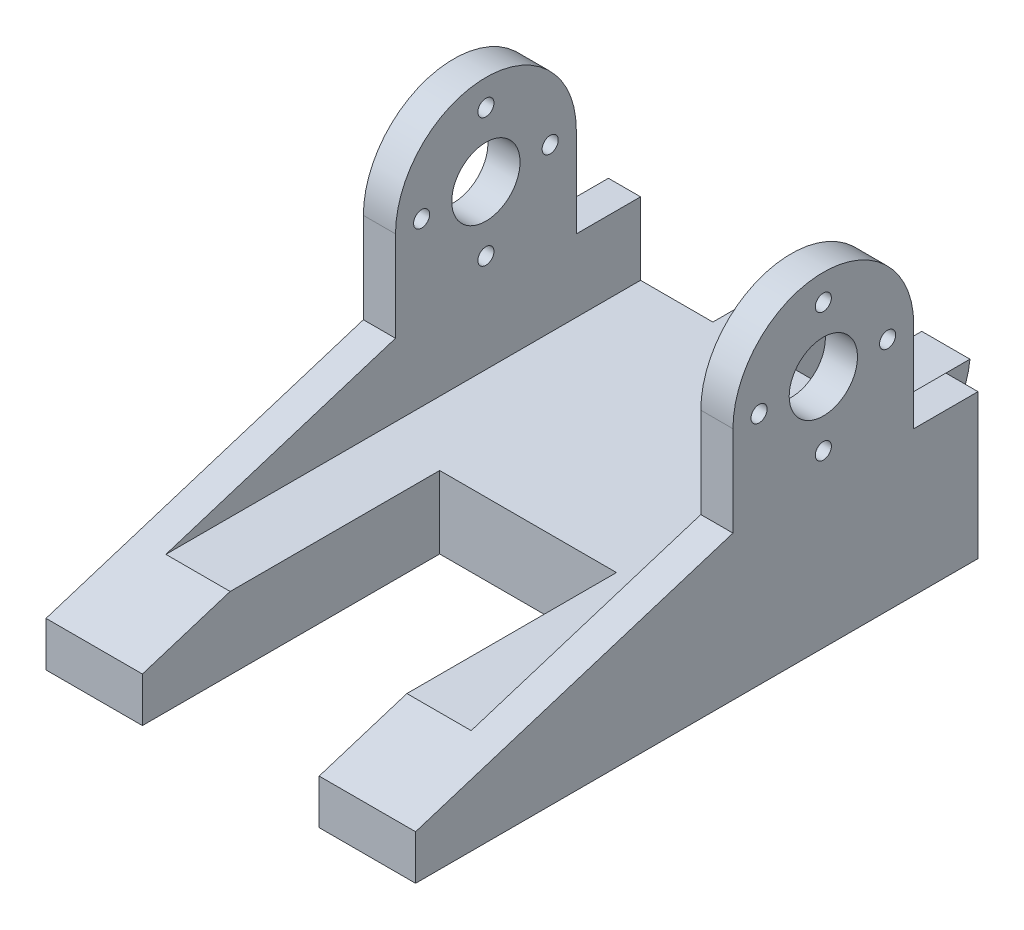
SolidWorks part; units mm, degrees
ref_plane "Front Plane" through (0, 0, 0) normal (0, 0, 1) x (1, 0, 0)
ref_plane "Top Plane" through (0, 0, 0) normal (0, 1, 0) x (1, 0, 0)
ref_plane "Right Plane" through (0, 0, 0) normal (1, 0, 0) x (0, 0, -1)
sketch "Sketch1" plane through (0, 0, 0) normal (0, 0, 1) x (1, 0, 0)
  line L1 (-25, 0) -> (25, 0)
  line L2 (-25, 0) -> (-25, -170)
  line L3 (-25, -170) -> (25, -170)
  line L4 (25, 0) -> (25, -170)
  dimension "D1" = 170
  dimension "D2" = 50
extrude "Boss-Extrude1" add sketch "Sketch1" against normal blind 55
sketch "Sketch2" plane through (0, 0, 0) normal (0, 0, 1) x (1, 0, 0)
  line L0 (25, 0) -> (-25, 0) construction
  line L1 (-17, 0) -> (17, 0)
  line L2 (-17, 0) -> (-17, -27)
  line L3 (-17, -27) -> (17, -27)
  line L4 (17, 0) -> (17, -27)
  line L5 (-25, 0) -> (-25, -170) construction
  dimension "D1" = 8
  dimension "D2" = 34
  dimension "D3" = 27
extrude "Cut-Extrude1" cut sketch "Sketch2" against normal through all
sketch "Sketch3" plane through (25, 0, 0) normal (1, 0, 0) x (0, 0, -1)
  line L0 (0, -170) -> (0, 0) construction
  line L1 (55, -27) -> (0, -27)
  line L2 (55, -27) -> (55, -24)
  line L3 (55, -24) -> (0, -24)
  line L4 (0, -27) -> (0, -24)
  line L5 (55, -170) -> (55, 0) construction
  line L7 (0, 0) -> (10, 0)
  line L8 (0, 0) -> (0, -24)
  line L9 (0, -24) -> (10, -24)
  line L10 (10, 0) -> (10, -24)
  line L11 (55, 0) -> (45, 0)
  line L12 (55, 0) -> (55, -24)
  line L13 (55, -24) -> (45, -24)
  line L14 (45, 0) -> (45, -24)
  circle A0 centre (27.5, -12.75) radius 10.25
  circle A1 centre (27.5, -12.75) radius 4.25
  circle A2 centre (27.5, -12.75) radius 8
  circle A3 centre (27.5, -4.75) radius 1
  circle A4 centre (35.5, -12.75) radius 1
  circle A5 centre (27.5, -20.75) radius 1
  circle A6 centre (19.5, -12.75) radius 1
  point P32 (27.5, -12.75)
  line M7 (0, 0) -> (0, -170)
  line M9 (55, -170) -> (55, 0)
  line M10 (55, 0) -> (0, 0)
  dimension "D2" = 11.25
  dimension "D3" = 27.5
  dimension "D4" = 20.5
  dimension "D7" = 8.5
  dimension "D8" = 16
  dimension "D9" = 4
  dimension "D1" = 3
  dimension "D5" = 10
  dimension "D6" = 10
extrude "Cut-Extrude2" cut sketch "Sketch3" against normal through all contours L14 L3 M10 M9 | L10 L3 M10 M7 | A2 A6 | A2 A6 | A1 | A2 A5 | A2 A5 | A2 A4 | A2 A4 | A2 A3 | A2 A3 region at (25, -12, -50) region at (25, -12, -5) region at (25, -12.75, -27.5) region at (25, -12.75, -35.0645) region at (25, -12.75, -35.913) region at (25, -5.1855, -27.5) region at (25, -4.337, -27.5) region at (25, -21.163, -27.5) region at (25, -20.3145, -27.5) region at (25, -12.75, -19.9355) region at (25, -12.75, -19.087)
sketch "Sketch4" plane through (0, 0, -10) normal (0, 0, 1) x (1, 0, 0)
  line L0 (-25, -24) -> (-17, -24) construction
  line L1 (-17, 0) -> (-19, 0)
  line L2 (-17, 0) -> (-17, -24)
  line L3 (-17, -24) -> (-19, -24)
  line L4 (-19, 0) -> (-19, -24)
  line L5 (0, 0) -> (0, -13.53) construction
  line L6 (19, 0) -> (19, -24)
  line L7 (17, -24) -> (19, -24)
  line L8 (17, 0) -> (17, -24)
  line L9 (17, 0) -> (19, 0)
  dimension "D1" = 2
extrude "Cut-Extrude3" cut sketch "Sketch4" against normal through all
sketch "Sketch5" plane through (25, 0, 0) normal (1, 0, 0) x (0, 0, -1)
  line L1 (10, 0) -> (45, 0)
  line L2 (10, 0) -> (10, -24)
  line L3 (10, -24) -> (45, -24)
  line L4 (45, 0) -> (45, -24)
  line L5 (38.75, -12.75) -> (38.75, -24)
  line L6 (16.25, -12.75) -> (10, -12.75)
  line L7 (16.25, -12.75) -> (16.25, -24)
  line L8 (16.25, -24) -> (10, -24)
  line L9 (10, -12.75) -> (10, -24)
  line L10 (38.75, -12.75) -> (45, -12.75)
  line L11 (38.75, -12.75) -> (38.75, -24)
  line L12 (38.75, -24) -> (45, -24)
  line L13 (45, -12.75) -> (45, -24)
  circle A0 centre (27.5, -12.75) radius 11.25
  line M8 (45, -24) -> (45, 0)
  line M9 (45, 0) -> (10, 0)
  line M10 (10, 0) -> (10, -24)
  dimension "D1" = 22.5
extrude "Cut-Extrude4" cut sketch "Sketch5" against normal through all contours A0 L10 L4 L6 M9 M10 | L7 L6 L2 L3 | L10 L5 L3 M8 region at (25, -0.3725, -27.5) region at (25, -18.375, -13.125) region at (25, -18.375, -41.875)
sketch "Sketch6" plane through (0, 0, 0) normal (0, 0, 1) x (1, 0, 0)
  line L1 (-19, -24) -> (19, -24)
  line L2 (-19, -24) -> (-19, -34)
  line L3 (-19, -34) -> (19, -34)
  line L4 (19, -24) -> (19, -34)
  dimension "D1" = 10
extrude "Cut-Extrude5" cut sketch "Sketch6" against normal through all
sketch "Sketch8" plane through (25, 0, 0) normal (1, 0, 0) x (0, 0, -1)
  line L0 (55, -170) -> (55, -24) construction
  line L1 (0, -170) -> (0, -24) construction
  line L2 (41.75, -132.5) -> (13.25, -132.5)
  line L3 (27.5, -132.5) -> (27.5, -179)
  line L4 (41.75, -179) -> (13.25, -179)
  line L5 (13.25, -132.5) -> (13.25, -179)
  line L7 (41.75, -132.5) -> (41.75, -179)
  line L11 (27.5, -167.75) -> (55, -167.75)
  line L12 (27.5, -167.75) -> (27.5, -170)
  line L13 (27.5, -170) -> (55, -170)
  line L14 (55, -167.75) -> (55, -170)
  line L16 (27.5, -167.75) -> (0, -167.75)
  line L17 (27.5, -167.75) -> (27.5, -170)
  line L18 (27.5, -170) -> (0, -170)
  line L19 (0, -167.75) -> (0, -170)
  circle A0 centre (27.5, -167.75) radius 10.25
  circle A1 centre (27.5, -12.75) radius 10.25
  line M4 (0, -24) -> (0, -170)
  line M5 (0, -170) -> (55, -170)
  line M6 (55, -170) -> (55, -24)
  dimension "D1" = 27.5
  dimension "D2" = 20.5
  dimension "D3" = 155
  dimension "D4" = 14.25
  dimension "D5" = 11.25
  dimension "D6" = 46.5
  dimension "D7" = 13.25
extrude "Cut-Extrude7" cut sketch "Sketch8" against normal through all contours A0 L3 L2 L5 L16 | A0 L11 L7 L2 L3 | L11 L7 M5 M6 | L5 L16 M4 M5 | A0 L16 L5 M5 | A0 L13 L7 L11 | L3 A0 L16 | L11 A0 L3 | L16 A0 L18 L3 | A0 L11 L3 M5 region at (25, -147.5157, -35.1704) region at (25, -147.5157, -19.8296) region at (25, -168.875, -48.375) region at (25, -168.8865, -39.7079) region at (25, -163.3998, -31.8502) region at (25, -163.3998, -23.1498) region at (25, -168.8704, -32.5838) region at (25, -168.8865, -15.2921) region at (25, -168.875, -6.625) region at (25, -168.8704, -22.4162)
sketch "Sketch9" plane through (0, 0, 0) normal (0, 0, 1) x (1, 0, 0)
  line L0 (-25, -167.75) -> (25, -167.75) construction
  line L1 (17, -167.75) -> (-17, -167.75)
  line L2 (17, -167.75) -> (17, -132.5)
  line L3 (17, -132.5) -> (-17, -132.5)
  line L4 (-17, -167.75) -> (-17, -132.5)
  line L5 (-25, -132.5) -> (25, -132.5) construction
  line L7 (-25, -24) -> (-25, -167.75) construction
  line L9 (25, -167.75) -> (25, -24) construction
  dimension "D1" = 8
  dimension "D2" = 8
extrude "Cut-Extrude8" cut sketch "Sketch9" against normal through all
sketch "Sketch11" plane through (25, 0, 0) normal (1, 0, 0) x (0, 0, -1)
  line L0 (27.5, -157.5) -> (27.5, -147.5)
  line L2 (27.5, -147.5) -> (55, -147.5)
  line L3 (27.5, -147.5) -> (27.5, -167.75)
  line L4 (27.5, -167.75) -> (55, -167.75)
  line L5 (55, -147.5) -> (55, -167.75)
  line L6 (27.5, -147.5) -> (0, -147.5)
  line L7 (27.5, -147.5) -> (27.5, -167.75)
  line L8 (27.5, -167.75) -> (0, -167.75)
  line L9 (0, -147.5) -> (0, -167.75)
  circle A0 centre (27.5, -167.75) radius 10.25
  arc A1 (38.75, -12.75) -> (16.25, -12.75) centre (27.5, -12.75) ccw construction
  line M1 (0, -167.75) -> (13.25, -167.75)
  line M2 (13.25, -167.75) -> (13.25, -132.5)
  line M4 (41.75, -132.5) -> (41.75, -167.75)
  line M5 (41.75, -167.75) -> (55, -167.75)
  line M6 (55, -167.75) -> (55, -24)
  line M12 (0, -24) -> (0, -167.75)
  dimension "D1" = 155
  dimension "D2" = 20.5
  dimension "D3" = 10
extrude "Cut-Extrude9" cut sketch "Sketch11" against normal through all contours A0 L0 L6 L8 M2 | A0 L4 L2 L0 M4 | L2 M4 M5 M6 | L6 M2 M12 M1 region at (25, -155.3124, -19.2638) region at (25, -155.3124, -35.7362) region at (25, -157.625, -48.375) region at (25, -157.625, -6.625)
sketch "Sketch12" plane through (25, 0, 0) normal (1, 0, 0) x (0, 0, -1)
  line L1 (13.25, -132.5) -> (41.75, -132.5)
  line L2 (13.25, -132.5) -> (13.25, -147.5)
  line L3 (13.25, -147.5) -> (41.75, -147.5)
  line L4 (41.75, -132.5) -> (41.75, -147.5)
extrude "Boss-Extrude2" add sketch "Sketch12" against normal blind 8
ref_plane "Plane1" through (0, 0, 0) normal (1, 0, 0) x (0, 0, -1)
mirror "Mirror1" about plane through (0, 0, 0) normal (1, 0, 0) of "Boss-Extrude2"
sketch "Sketch14" plane through (0, 0, 0) normal (0, 0, 1) x (1, 0, 0)
  line L0 (17, -148.55) -> (17, -158.75) construction
  line L1 (-17, -132.5) -> (17, -132.5)
  line L2 (-17, -132.5) -> (-17, -147.5)
  line L3 (-17, -147.5) -> (17, -147.5)
  line L4 (17, -132.5) -> (17, -147.5)
  line L5 (-17, -147.5) -> (17, -147.5)
  line L6 (-17, -147.5) -> (-17, -157.75)
  line L7 (-17, -157.75) -> (17, -157.75)
  line L8 (17, -147.5) -> (17, -157.75)
  line M11 (-17, -147.5) -> (-17, -132.5)
  line M12 (-17, -132.5) -> (17, -132.5)
  line M13 (17, -132.5) -> (17, -147.5)
  dimension "D1" = 10.25
extrude "Boss-Extrude3" add sketch "Sketch14" against normal blind 13.25 contours L3 M11 M13 M12 | L8 L3 L6 L7 region at (0, -140, 0) region at (0, -152.625, 0)
ref_plane "Plane2" through (0, 0, -27.5) normal (0, 0, 1) x (1, 0, 0)
mirror "Mirror2" about plane through (0, 0, -27.5) normal (0, 0, 1) of "Boss-Extrude3"
sketch "Sketch16" plane through (25, 0, 0) normal (1, 0, 0) x (0, 0, -1)
  line L0 (41.75, -132.5) -> (13.25, -132.5) construction
  line L1 (13.25, -132.5) -> (13.25, -147.5) construction
  circle A1 centre (16.5, -135.75) radius 2.5
  circle A2 centre (16.5, -135.75) radius 4.5
  circle A3 centre (38.5, -135.75) radius 4.5
  dimension "D1" = 3.25
  dimension "D2" = 3.25
  dimension "D3" = 2
extrude "Cut-Extrude13" cut sketch "Sketch16" against normal blind 8 contours A1 | A2 A1 | A3 region at (25, -135.75, -16.5) region at (25, -135.75, -12.1273) region at (25, -135.75, -38.5)
mirror "Mirror3" about plane through (0, 0, 0) normal (1, 0, 0) of "Cut-Extrude13"
sketch "Sketch17" plane through (25, 0, 0) normal (1, 0, 0) x (0, 0, -1)
  line L0 (55, -147.5) -> (55, -24) construction
  line L1 (27.5, -1.5) -> (55, -1.5)
  line L2 (27.5, -1.5) -> (27.5, -51.5)
  line L3 (27.5, -51.5) -> (55, -51.5)
  line L4 (55, -1.5) -> (55, -51.5)
  line L8 (55, -51.5) -> (0, -51.5)
  line L9 (55, -51.5) -> (55, -157.75)
  line L10 (55, -157.75) -> (0, -157.75)
  line L11 (0, -51.5) -> (0, -157.75)
  arc A0 (38.75, -12.75) -> (16.25, -12.75) centre (27.5, -12.75) ccw construction
  circle M2 centre (16.5, -135.75) radius 4.5
  circle M3 centre (38.5, -135.75) radius 4.5
  line M4 (0, -147.5) -> (55, -147.5)
  line M5 (55, -147.5) -> (55, -24)
  line M11 (0, -24) -> (0, -147.5)
  dimension "D1" = 50
extrude "Cut-Extrude15" cut sketch "Sketch17" against normal through all contours L3 L8 M11 M4 M5 M2 M3 | L11 L10 L9 M4 | M3 | M2 region at (25, -98.6049, -27.5) region at (25, -152.625, -27.5) region at (25, -135.75, -16.5) region at (25, -135.75, -38.5)
sketch "Sketch18" plane through (25, 0, 0) normal (1, 0, 0) x (0, 0, -1)
  line L1 (38.75, -24) -> (-71.25, -24)
  line L2 (38.75, -24) -> (38.75, -51.5)
  line L3 (38.75, -51.5) -> (-71.25, -51.5)
  line L4 (-71.25, -24) -> (-71.25, -51.5)
  line L6 (38.75, -24) -> (68.75, -24)
  line L7 (38.75, -24) -> (38.75, -51.5)
  line L8 (38.75, -51.5) -> (68.75, -51.5)
  line L9 (68.75, -24) -> (68.75, -51.5)
  line M8 (0, -24) -> (0, -51.5)
  line M9 (0, -51.5) -> (55, -51.5)
  line M10 (55, -51.5) -> (55, -24)
  line M11 (55, -24) -> (38.75, -24)
  line M15 (16.25, -24) -> (0, -24)
  dimension "D1" = 110
  dimension "D2" = 30
extrude "Boss-Extrude4" add sketch "Sketch18" against normal blind 50 contours L1 L4 L3 M8 | L9 L6 L8 M10 | L2 L1 M15 M8 M9 | L2 M11 M9 M10 region at (25, -37.75, -19.375) region at (25, -37.75, -46.875) region at (25, -37.75, -61.875) region at (25, -37.75, 35.625)
sketch "Sketch19" plane through (0, 0, 71.25) normal (0, 0, 1) x (1, 0, 0)
  line L1 (-19, -24) -> (19, -24)
  line L2 (-19, -24) -> (-19, -31)
  line L3 (-19, -31) -> (19, -31)
  line L4 (19, -24) -> (19, -31)
  dimension "D1" = 7
extrude "Cut-Extrude16" cut sketch "Sketch19" against normal through all
sketch "Sketch20" plane through (25, 0, 0) normal (1, 0, 0) x (0, 0, -1)
  line L1 (-71.25, -24) -> (68.75, -24)
  line L2 (-71.25, -24) -> (-71.25, -51.5)
  line L3 (-71.25, -51.5) -> (68.75, -51.5)
  line L4 (68.75, -24) -> (68.75, -51.5)
  line L5 (16.25, -24) -> (-13.75, -24)
  line L6 (16.25, -24) -> (16.25, -51.5)
  line L7 (16.25, -51.5) -> (-13.75, -51.5)
  line L8 (-13.75, -24) -> (-13.75, -51.5)
  line L10 (-13.75, -51.5) -> (-71.25, -51.5)
  line L11 (-13.75, -51.5) -> (-13.75, -24)
  line L12 (-13.75, -24) -> (-71.25, -24)
  line L13 (-71.25, -51.5) -> (-71.25, -24)
  line M8 (-71.25, -24) -> (-71.25, -51.5)
  line M9 (-71.25, -51.5) -> (68.75, -51.5)
  dimension "D1" = 30
extrude "Cut-Extrude17" cut sketch "Sketch20" against normal through all contours L8 L1 M8 M9 region at (25, -37.75, 42.5)
sketch "Sketch21" plane through (25, 0, 0) normal (1, 0, 0) x (0, 0, -1)
  line L0 (16.25, -24) -> (-13.75, -51.5)
  line L1 (16.25, -24) -> (-13.75, -24)
  line L2 (16.25, -24) -> (16.25, -51.5)
  line L3 (16.25, -51.5) -> (-13.75, -51.5)
  line L4 (-13.75, -24) -> (-13.75, -51.5)
  line M6 (16.25, -24) -> (-13.75, -24)
  line M7 (-13.75, -24) -> (-13.75, -51.5)
extrude "Cut-Extrude18" cut sketch "Sketch21" against normal through all contours L0 M6 M7 region at (25, -33.1667, 3.75)
sketch "Sketch22" plane through (25, 0, 0) normal (1, 0, 0) x (0, 0, -1)
  line L3 (68.75, -51.5) -> (-13.75, -51.5)
  line L4 (68.75, -51.5) -> (68.75, -54)
  line L5 (68.75, -54) -> (-13.75, -54)
  line L6 (-13.75, -51.5) -> (-13.75, -54)
  dimension "D1" = 2.5
extrude "Boss-Extrude5" add sketch "Sketch22" against normal blind 50
sketch "Sketch24" plane through (25, 0, 0) normal (1, 0, 0) x (0, 0, -1)
  line L1 (68.75, -24) -> (46.75, -24)
  line L2 (68.75, -24) -> (68.75, -41)
  line L3 (68.75, -41) -> (46.75, -41)
  line L4 (46.75, -24) -> (46.75, -41)
  dimension "D1" = 17
  dimension "D2" = 22
extrude "Cut-Extrude19" cut sketch "Sketch24" against normal through all
sketch "Sketch25" plane through (0, -31, 0) normal (0, 1, 0) x (1, 0, 0)
  line L1 (-19, 46.75) -> (19, 46.75)
  line L2 (-19, 46.75) -> (-19, 8.6136)
  line L3 (-19, 8.6136) -> (19, 8.6136)
  line L4 (19, 46.75) -> (19, 8.6136)
extrude "Cut-Extrude20" cut sketch "Sketch25" against normal blind 10
sketch "Sketch27" plane through (0, -41, 0) normal (0, 1, 0) x (1, 0, 0)
  line L0 (-25, 68.75) -> (25, 68.75) construction
  line L1 (19, 8.6136) -> (-19, 8.6136)
  line L2 (19, 8.6136) -> (19, 68.75)
  line L3 (19, 68.75) -> (-19, 68.75)
  line L4 (-19, 8.6136) -> (-19, 68.75)
extrude "Boss-Extrude6" add sketch "Sketch27" along normal blind 8.6
sketch "Sketch29" plane through (0, 0, -8.6136) normal (0, 0, -1) x (-1, 0, 0)
  line L1 (-19, -31) -> (19, -31)
  line L2 (-19, -31) -> (-19, -32.4)
  line L3 (-19, -32.4) -> (19, -32.4)
  line L4 (19, -31) -> (19, -32.4)
extrude "Cut-Extrude21" cut sketch "Sketch29" against normal through all
sketch "Sketch30" plane through (-25, 0, 0) normal (-1, 0, 0) x (0, 0, 1)
  line L0 (-68.75, -32.4) -> (-68.75, -41) construction
  line L1 (-38.75, -24) -> (31.25, -24)
  line L2 (-38.75, -24) -> (-38.75, -53.9144)
  line L3 (-38.75, -53.9144) -> (31.25, -53.9144)
  line L4 (31.25, -24) -> (31.25, -53.9144)
  line L5 (-16.25, -24) -> (31.25, -38.9572)
  line L6 (31.25, -38.9572) -> (31.25, -53.9144)
  line L7 (-16.25, -24) -> (-16.25, -32.4)
  line L8 (-46.75, -32.4) -> (-7.0864, -32.4) construction
  line L9 (-16.25, -32.4) -> (-7.0864, -32.4)
  line L10 (-7.0864, -32.4) -> (-16.25, -24)
  line M5 (13.75, -54) -> (13.75, -51.5)
  line M6 (13.75, -51.5) -> (-16.25, -24)
  dimension "D1" = 100
extrude "Boss-Extrude7" add sketch "Sketch30" against normal blind 50 contours L5 L3 L4 M6 M5 | L7 L9 L10 region at (-25, -40.9436, 13.5151)
sketch "Sketch31" plane through (0, 0, -68.75) normal (0, 0, -1) x (-1, 0, 0)
  line L1 (-19, -24) -> (19, -24)
  line L2 (-19, -24) -> (-19, -41)
  line L3 (-19, -41) -> (19, -41)
  line L4 (19, -24) -> (19, -41)
extrude "Cut-Extrude22" cut sketch "Sketch31" against normal through all
sketch "Sketch32" plane through (25, 0, 0) normal (1, 0, 0) x (0, 0, -1)
  line L0 (-31.25, -38.9572) -> (-31.25, -53.9144) construction
  line L1 (68.75, -54) -> (-31.25, -54)
  line L2 (68.75, -54) -> (68.75, -51)
  line L3 (68.75, -51) -> (-31.25, -51)
  line L4 (-31.25, -54) -> (-31.25, -51)
  dimension "D1" = 3
extrude "Cut-Extrude23" cut sketch "Sketch32" against normal through all
sketch "Sketch33" plane through (0, -41, 0) normal (0, 1, 0) x (1, 0, 0)
  line L0 (19, -31.25) -> (-19, -31.25) construction
  line L1 (11, -31.25) -> (-11, -31.25)
  line L2 (11, -31.25) -> (11, 13.75)
  line L3 (11, 13.75) -> (-11, 13.75)
  line L4 (-11, -31.25) -> (-11, 13.75)
  line L6 (-25, 68.75) -> (-10, 68.75)
  line L7 (-25, 68.75) -> (-25, 46.75)
  line L8 (-25, 46.75) -> (-10, 46.75)
  line L9 (-10, 68.75) -> (-10, 46.75)
  line L10 (25, 68.75) -> (10, 68.75)
  line L11 (25, 68.75) -> (25, 46.75)
  line L12 (25, 46.75) -> (10, 46.75)
  line L13 (10, 68.75) -> (10, 46.75)
  line L15 (19, 16.25) -> (19, -31.25) construction
  line L16 (-19, -31.25) -> (-19, 46.75) construction
  line L18 (-10, 68.75) -> (10, 68.75)
  line L19 (-10, 68.75) -> (-10, 58.75)
  line L20 (-10, 58.75) -> (10, 58.75)
  line L21 (10, 68.75) -> (10, 58.75)
  line M10 (-25, 46.75) -> (-19, 46.75)
  line M12 (-19, -31.25) -> (19, -31.25)
  line M14 (19, 46.75) -> (25, 46.75)
  line M15 (25, 46.75) -> (25, 68.75)
  line M16 (25, 68.75) -> (-25, 68.75)
  line M17 (-25, 68.75) -> (-25, 46.75)
  dimension "D1" = 8
  dimension "D2" = 8
  dimension "D3" = 45
  dimension "D4" = 15
  dimension "D5" = 15
  dimension "D6" = 10
extrude "Cut-Extrude24" cut sketch "Sketch33" against normal through all contours L9 L8 M16 M17 M10 | L13 L12 M16 M14 M15 | L9 L20 L13 M16 | L4 L2 L3 M12 region at (0, -41, 8.75) region at (-17.5, -41, -57.75) region at (0, -41, -63.75) region at (17.5, -41, -57.75)
sketch "Sketch34" plane through (0, -41, 0) normal (0, 1, 0) x (1, 0, 0)
  line L0 (-10, 58.75) -> (10, 58.75) construction
  line L1 (-4, 58.75) -> (4, 58.75)
  line L2 (-4, 58.75) -> (-4, 46.75)
  line L3 (-4, 46.75) -> (4, 46.75)
  line L4 (4, 58.75) -> (4, 46.75)
  line L5 (-10, 58.75) -> (-10, 46.75) construction
  line L6 (10, 58.75) -> (10, 46.75) construction
  dimension "D1" = 6
  dimension "D2" = 6
  dimension "D3" = 12
extrude "Cut-Extrude25" cut sketch "Sketch34" against normal through all
sketch "Sketch36" plane through (0, -41, 0) normal (0, 1, 0) x (1, 0, 0)
  line L1 (19, -31.25) -> (-19, -31.25)
  line L2 (19, -31.25) -> (19, 58.75)
  line L3 (19, 58.75) -> (-19, 58.75)
  line L4 (-19, -31.25) -> (-19, 58.75)
  line L5 (-4, 58.75) -> (4, 58.75)
  line L6 (-4, 58.75) -> (-4, 46.75)
  line L7 (-4, 46.75) -> (4, 46.75)
  line L8 (4, 58.75) -> (4, 46.75)
  line L9 (10, 58.75) -> (19, 58.75)
  line L10 (10, 58.75) -> (10, 46.75)
  line L11 (10, 46.75) -> (19, 46.75)
  line L12 (19, 58.75) -> (19, 46.75)
  line L13 (-10, 58.75) -> (-19, 58.75)
  line L14 (-10, 58.75) -> (-10, 46.75)
  line L15 (-10, 46.75) -> (-19, 46.75)
  line L16 (-19, 58.75) -> (-19, 46.75)
  line L17 (-11, 13.75) -> (11, 13.75)
  line L18 (-11, 13.75) -> (-11, -31.25)
  line L19 (-11, -31.25) -> (11, -31.25)
  line L20 (11, 13.75) -> (11, -31.25)
  line M1 (4, 46.75) -> (-4, 46.75)
  line M2 (-4, 46.75) -> (-4, 58.75)
  line M3 (-4, 58.75) -> (-10, 58.75)
  line M4 (-10, 58.75) -> (-10, 46.75)
  line M5 (-10, 46.75) -> (-19, 46.75)
  line M6 (-19, 46.75) -> (-19, -31.25)
  line M7 (-19, -31.25) -> (-11, -31.25)
  line M8 (-11, -31.25) -> (-11, 13.75)
  line M9 (-11, 13.75) -> (11, 13.75)
  line M10 (11, 13.75) -> (11, -31.25)
  line M11 (11, -31.25) -> (19, -31.25)
  line M12 (19, -31.25) -> (19, 46.75)
  line M13 (19, 46.75) -> (10, 46.75)
  line M14 (10, 46.75) -> (10, 58.75)
  line M15 (10, 58.75) -> (4, 58.75)
  line M16 (4, 58.75) -> (4, 46.75)
extrude "Boss-Extrude8" add sketch "Sketch36" along normal blind 8 contours M16 M1 M2 M3 M4 M5 M6 M7 M8 M9 M10 M11 M12 M13 M14 M15 region at (0, -41, -18.522)
sketch "Sketch37" plane through (25, 0, 0) normal (1, 0, 0) x (0, 0, -1)
  line L0 (-31.25, -38.9572) -> (-31.25, -51) construction
  line L1 (58.75, -51) -> (-31.25, -51)
  line L2 (58.75, -51) -> (58.75, -42)
  line L3 (58.75, -42) -> (-31.25, -42)
  line L4 (-31.25, -51) -> (-31.25, -42)
  line L5 (-31.25, -38.9572) -> (-12.3315, -33)
  line L6 (-12.3315, -33) -> (-31.25, -33)
  line L7 (-12.3315, -33) -> (-12.3315, -38.9572)
  line L8 (-12.3315, -38.9572) -> (-31.25, -38.9572)
  line L9 (-31.25, -33) -> (-31.25, -38.9572)
  line L11 (58.75, -42) -> (46.75, -42)
  line L12 (58.75, -42) -> (58.75, -51)
  line L13 (58.75, -51) -> (46.75, -51)
  line L14 (46.75, -42) -> (46.75, -51)
  line M7 (-31.25, -51) -> (46.75, -51)
  line M8 (46.75, -51) -> (46.75, -24)
  line M13 (16.25, -24) -> (-31.25, -38.9572)
  line M14 (-31.25, -38.9572) -> (-31.25, -51)
  dimension "D1" = 9
extrude "Cut-Extrude27" cut sketch "Sketch37" against normal through all contours L3 M8 M14 M7 | L6 L9 M13 | L2 L3 L1 M8 region at (25, -34.9857, 24.9438) region at (25, -46.5, -52.75) region at (25, -46.5, -7.75)
fillet "Fillet1" radius 10 2 edges at (-7, -42, -58.75) (7, -42, -58.75)
sketch "Sketch38" plane through (0, 0, 0) normal (0, 1, 0) x (1, 0, 0)
  line L6 (-11, -31.25) -> (-25, -31.25) construction
  line L7 (-25, 46.75) -> (-23, 46.75)
  line L8 (-25, 46.75) -> (-25, -31.25)
  line L9 (-25, -31.25) -> (-23, -31.25)
  line L10 (-23, 46.75) -> (-23, -31.25)
  line L11 (25, -31.25) -> (11, -31.25) construction
  line L12 (25, 46.75) -> (23, 46.75)
  line L13 (25, 46.75) -> (25, -31.25)
  line L14 (25, -31.25) -> (23, -31.25)
  line L15 (23, 46.75) -> (23, -31.25)
  line L17 (-23, -31.25) -> (23, -31.25)
  line L18 (-23, -31.25) -> (-23, -23.25)
  line L19 (-23, -23.25) -> (23, -23.25)
  line L20 (23, -31.25) -> (23, -23.25)
  dimension "D1" = 2
  dimension "D2" = 2
  dimension "D3" = 8
extrude "Cut-Extrude29" cut sketch "Sketch38" against normal through all both and the other way through all contours L10 L7 L8 L9 | L12 L15 L14 L13 | L19 L10 L17 L15 region at (-24, 0, -7.75) region at (0, 0, 27.25) region at (24, 0, -7.75)
